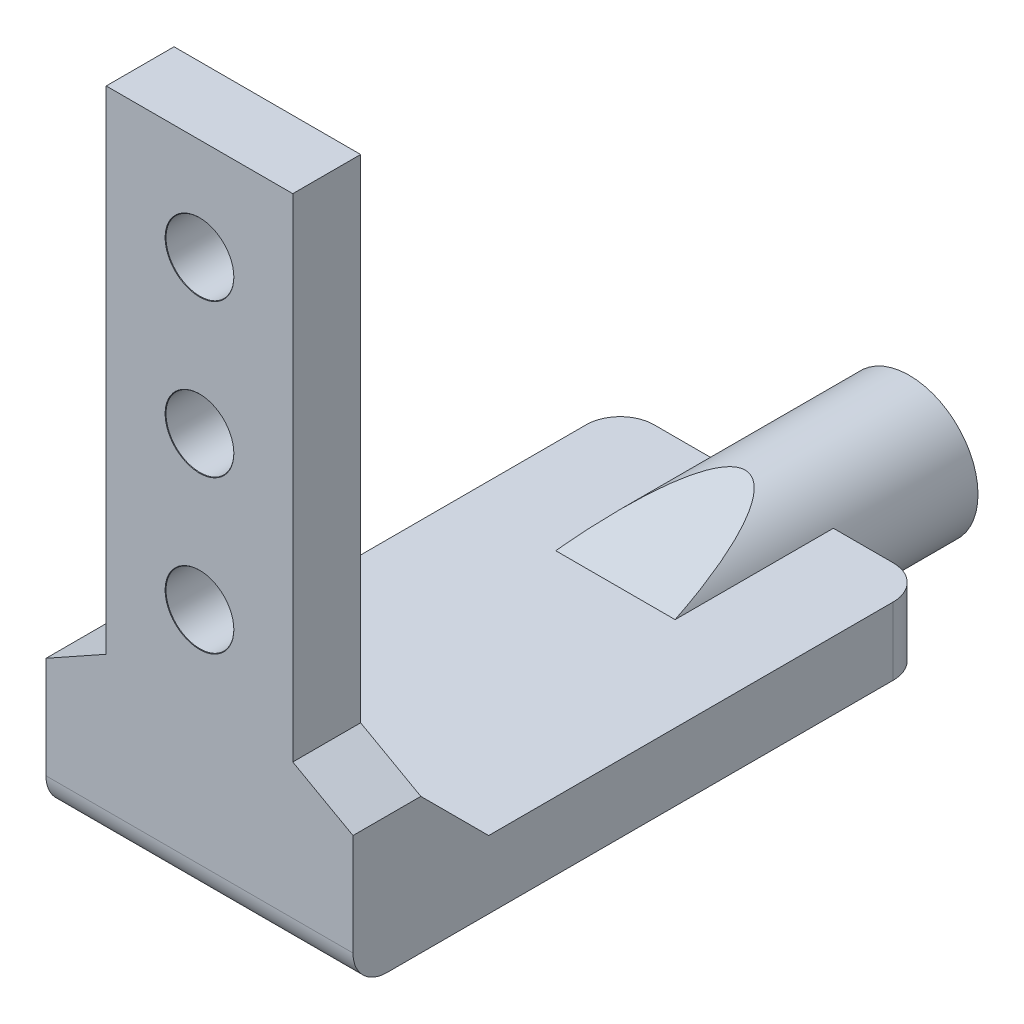
SolidWorks part; units mm, degrees
material "ABS"
ref_plane "Front Plane" through (0, 0, 0) normal (0, 0, 1) x (1, 0, 0)
ref_plane "Top Plane" through (0, 0, 0) normal (0, 1, 0) x (1, 0, 0)
ref_plane "Right Plane" through (0, 0, 0) normal (1, 0, 0) x (0, 0, -1)
sketch "Sketch1" plane through (0, 0, 0) normal (0, 0, 1) x (1, 0, 0)
  circle A0 centre (0, 0) radius 4.05
  dimension "D1" = 8.1
extrude "Boss-Extrude1" add sketch "Sketch1" along normal blind 8
sketch "Sketch2" plane through (0, 0, 8) normal (0, 0, 1) x (1, 0, 0)
  line L1 (-9.05, -2) -> (9.05, -2)
  line L2 (-9.05, -2) -> (-9.05, 2)
  line L3 (-9.05, 2) -> (9.05, 2)
  line L4 (9.05, -2) -> (9.05, 2)
  line L5 (-9.05, -2) -> (9.05, 2) construction
  line L6 (-9.05, 2) -> (9.05, -2) construction
  point P0 (0, 0)
  dimension "D1" = 4
  dimension "D2" = 18.1
extrude "Boss-Extrude2" add sketch "Sketch2" along normal blind 33.85
chamfer "Chamfer1" distance 2.5 angle 75 1 edges at (0, 2, 8) first distance on face at (0, 3.025, 8)
chamfer "Chamfer2" distance 2.5 angle 75 1 edges at (0, -2, 8) first distance on face at (0, -3.025, 8)
fillet "Fillet1" radius 2 2 edges at (-9.05, 0, 8) (9.05, 0, 8)
sketch "Sketch3" plane through (0, 2, 0) normal (0, 1, 0) x (1, 0, 0)
  line L0 (9.05, -41.85) -> (9.05, -10) construction
  line L1 (-9.05, -41.85) -> (9.05, -41.85)
  line L2 (-9.05, -41.85) -> (-9.05, -37.85)
  line L3 (-9.05, -37.85) -> (9.05, -37.85)
  line L4 (9.05, -41.85) -> (9.05, -37.85)
  dimension "D1" = 4
extrude "Boss-Extrude3" add sketch "Sketch3" along normal blind 35
chamfer "Chamfer3" distance 4 angle 45 1 edges at (0, 2, 37.85)
hole_wizard "Ø4.0mm Dowel Hole1" positions "Sketch4" profile "Sketch5" hole size "Ø4.0" standard "ANSI Metric" end condition through all
sketch "Sketch4" plane through (0, 0, 41.85) normal (0, 0, 1) x (1, 0, 0)
  line L0 (-9.05, 37) -> (9.05, 37) construction
  point P0 (0, 31)
  point P2 (0, 22)
  point P4 (0, 13)
  dimension "D1" = 6
  dimension "D2" = 9
  dimension "D3" = 9
sketch "Sketch5" plane through (0, 31, 41.85) normal (1, 0, 0) x (0, -1, 0)
  line L0 (0, 0) -> (0, 41.85)
  line L1 (0, 41.85) -> (2, 41.85)
  line L2 (2, 41.85) -> (2, 0.025)
  line L3 (2, 0.025) -> (2.025, 0)
  line L5 (2.025, 0) -> (0, 0)
  line L6 (-2, 0.025) -> (-2.025, 0) construction
  line L11 (0, -6.35) -> (0, 107.95) construction
  dimension "Thru Hole Dia." = 4
  dimension "Thru Hole Depth" = 41.85
  dimension "Near C'Sink Dia." = 4.05
  dimension "Near C'Sink Angle" = 90
fillet "Fillet2" radius 2 1 edges at (0, -2, 41.85)
sketch "Sketch6" plane through (0, 0, 37.85) normal (0, 0, -1) x (-1, 0, 0)
  line L0 (-9.05, 6) -> (-5.5, 7.98)
  line L1 (-5.5, 7.98) -> (-5.5, 37)
  line L2 (-9.05, 37) -> (9.05, 37) construction
  line L3 (-5.5, 37) -> (-9.05, 37)
  line L4 (-9.05, 37) -> (-9.05, 6)
  line L5 (-9.05, 6) -> (9.05, 6) construction
  dimension "D1" = 3.55
  dimension "D2" = 1.98
extrude "Cut-Extrude1" cut sketch "Sketch6" against normal through all both
sketch "Sketch7" plane through (0, 0, 37.85) normal (0, 0, -1) x (-1, 0, 0)
  line L0 (9.05, 6) -> (5.5, 7.98)
  line L1 (5.5, 7.98) -> (5.5, 37)
  line L2 (-5.5, 37) -> (9.05, 37) construction
  line L3 (5.5, 37) -> (9.05, 37)
  line L4 (9.05, 37) -> (9.05, 6)
  line L5 (-9.05, 6) -> (9.05, 6) construction
  dimension "D1" = 3.55
  dimension "D2" = 1.98
extrude "Cut-Extrude2" cut sketch "Sketch7" against normal through all both
